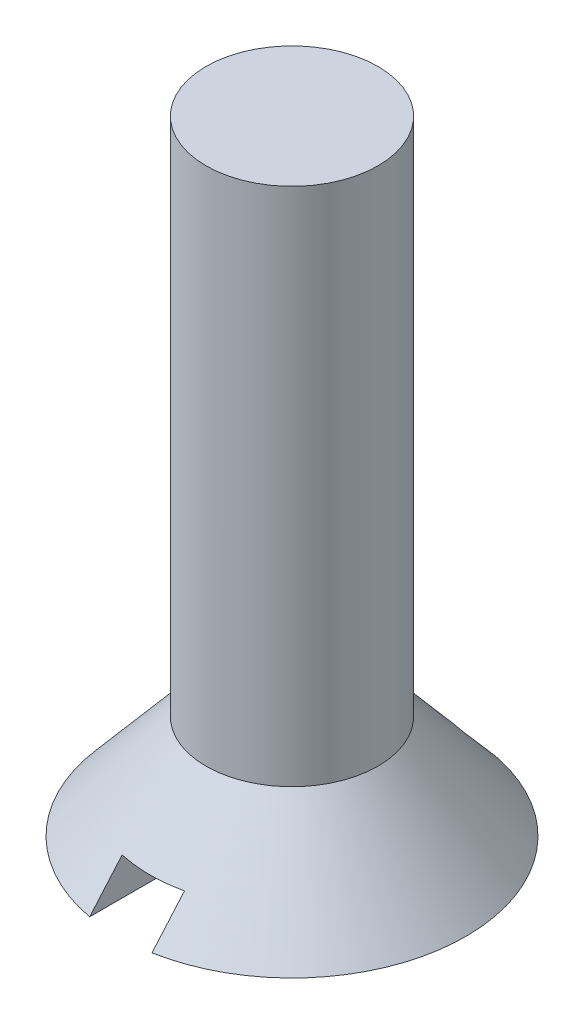
SolidWorks part; units mm, degrees
ref_plane "Front Plane" through (0, 0, 0) normal (0, 0, 1) x (1, 0, 0)
ref_plane "Top Plane" through (0, 0, 0) normal (0, 1, 0) x (1, 0, 0)
ref_plane "Right Plane" through (0, 0, 0) normal (1, 0, 0) x (0, 0, -1)
sketch "Sketch1" plane through (0, 0, 0) normal (0, 1, 0) x (1, 0, 0)
  circle A0 centre (0, 0) radius 3.5433
  dimension "D1" = 7.0866
sketch "Sketch2" plane through (0, 0, 0) normal (0, 0, 1) x (1, 0, 0)
  line L0 (3.5433, 0) -> (-3.5433, 0) construction
  line L1 (3.5433, 0) -> (0, 0)
  line L4 (0, 2.1082) -> (1.7526, 2.1082)
  line L5 (1.7526, 2.1082) -> (3.5433, 0)
  line L6 (0, 2.1082) -> (0, 0)
  dimension "D1" = 2.1082
  dimension "D3" = 1.7526
revolve "Revolve2" add sketch "Sketch2" angle 360 about L6
sketch "Sketch3" plane through (0, 2.1082, 0) normal (0, 1, 0) x (-1, 0, 0)
  circle A0 centre (0, 0) radius 1.7526
  circle A1 centre (0, 0) radius 3.5433 construction
extrude "Boss-Extrude1" add sketch "Sketch3" along normal blind 10.5918
sketch "Sketch4" plane through (0, 0, 0) normal (0, 0, 1) x (1, 0, 0)
  line L0 (0, 0) -> (0.635, 0)
  line L1 (3.5433, 0) -> (-3.5433, 0) construction
  line L2 (0.635, 0) -> (0.635, 0.762)
  line L3 (0.635, 0.762) -> (0.1238, 0.762)
  line L4 (0.1238, 0.762) -> (-0.635, 0.762)
  line L5 (-0.635, 0.762) -> (-0.635, 0)
  line L6 (-0.635, 0) -> (0, 0)
  dimension "D1" = 1.27
  dimension "D2" = 0.635
  dimension "D3" = 0.635
  dimension "D4" = 0.762
extrude "Cut-Extrude1" cut sketch "Sketch4" along normal blind 4.1148 and the other way blind 4.572
